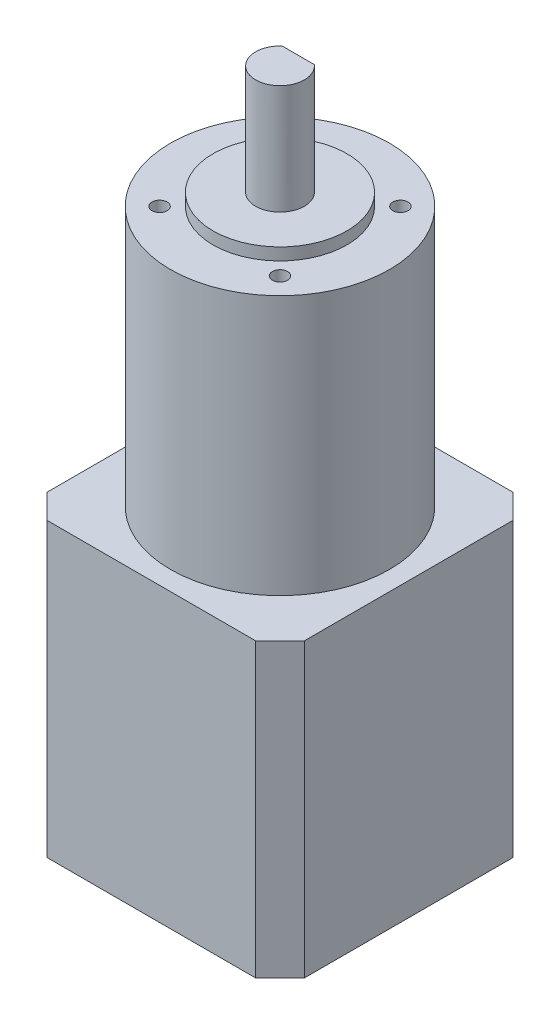
SolidWorks part; units mm, degrees
ref_plane "Plan de face" through (0, 0, 0) normal (0, 0, 1) x (1, 0, 0)
ref_plane "Plan de dessus" through (0, 0, 0) normal (0, 1, 0) x (1, 0, 0)
ref_plane "Plan de droite" through (0, 0, 0) normal (1, 0, 0) x (0, 0, -1)
sketch "Esquisse1" plane through (0, 0, 0) normal (0, 1, 0) x (1, 0, 0)
  line L1 (-21.15, 21.15) -> (21.15, 21.15)
  line L2 (-21.15, 21.15) -> (-21.15, -21.15)
  line L3 (-21.15, -21.15) -> (21.15, -21.15)
  line L4 (21.15, 21.15) -> (21.15, -21.15)
  point P4 (0, 21.15)
  point P6 (-21.15, 0)
  dimension "D1" = 42.3
  dimension "D2" = 42.3
extrude "Moteur" add sketch "Esquisse1" against normal blind 48
chamfer "Chanfrein1" distance 4 angle 45 4 edges at (21.15, -24, -21.15) (-21.15, -24, -21.15) (-21.15, -24, 21.15) (21.15, -24, 21.15)
sketch "Esquisse2" plane through (0, 0, 0) normal (0, 1, 0) x (1, 0, 0)
  circle A0 centre (0, 0) radius 18
  dimension "D1" = 36
extrude "Boss.-Extru.2" add sketch "Esquisse2" along normal blind 42.7
sketch "Esquisse3" plane through (0, 42.7, 0) normal (0, 1, 0) x (1, 0, 0)
  circle A0 centre (0, 0) radius 11
  dimension "D1" = 22
extrude "Boss.-Extru.3" add sketch "Esquisse3" along normal blind 2
sketch "Esquisse4" plane through (0, 44.7, 0) normal (0, 1, 0) x (1, 0, 0)
  circle A0 centre (0, 0) radius 4
  dimension "D1" = 8
extrude "Boss.-Extru.4" add sketch "Esquisse4" along normal blind 18
sketch "Esquisse5" plane through (0, 62.7, 0) normal (0, 1, 0) x (1, 0, 0)
  line L1 (-2.6458, 4) -> (2.6458, 4)
  line L2 (-2.6458, 4) -> (-2.6458, 3)
  line L3 (-2.6458, 3) -> (2.6458, 3)
  line L4 (2.6458, 4) -> (2.6458, 3)
  circle A0 centre (0, 0) radius 4 construction
  circle A1 centre (0, 0) radius 4 construction
  point P4 (0, 0)
  point P7 (0, 0)
  dimension "D1" = 1
extrude "Enlèv. mat.-Extru.1" cut sketch "Esquisse5" against normal blind 15
hole_wizard "Trou pour taraudage pour trou taraudé M3x0.51" positions "Esquisse6" profile "Esquisse7" hole size "M3x0.5" standard "Ansi Metric"
sketch "Esquisse6" plane through (0, 42.7, 0) normal (0, 1, 0) x (1, 0, 0)
  line L0 (0, 0) -> (0, 14) construction
  line L2 (0, 0) -> (-9.8995, 9.8995) construction
  circle A0 centre (0, 0) radius 14 construction
  point P0 (-9.8995, 9.8995)
  dimension "D1" = 28
  dimension "D2" = 45
sketch "Esquisse7" plane through (-9.8995, 42.7, -9.8995) normal (1, 0, 0) x (0, 0, 1)
  line L0 (0, 0) -> (0, 5.7511)
  line L1 (0, 5.7511) -> (1.25, 5)
  line L2 (1.25, 5) -> (1.25, 0)
  line L5 (1.25, 0) -> (0, 0)
  line L10 (0, 5.7511) -> (-1.25, 5) construction
  line L11 (0, -6.35) -> (0, 107.95) construction
  dimension "Diamètre du perçage" = 2.5
  dimension "Profondeur du perçage" = 5
  dimension "Angle de pointe" = 118
ref_axis "motor_axis" through (0, 69.928, 0) along (0, -1, 0)
pattern_circular "Répétition circulaire1" count 4 over 360 about axis through (0, 69.928, 0) along (0, -1, 0) of "Trou pour taraudage pour trou taraudé M3x0.51"
